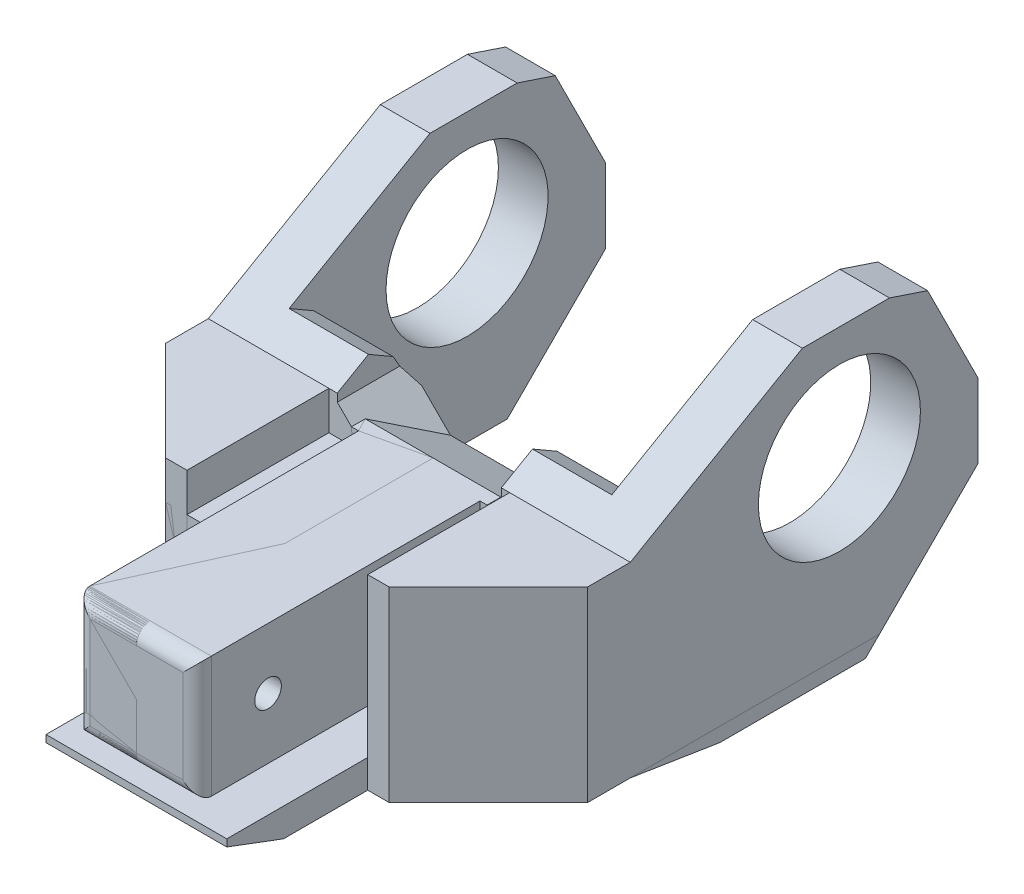
SolidWorks part; units mm, degrees
ref_plane "Front Plane" through (0, 0, 0) normal (0, 0, 1) x (1, 0, 0)
ref_plane "Top Plane" through (0, 0, 0) normal (0, 1, 0) x (1, 0, 0)
ref_plane "Right Plane" through (0, 0, 0) normal (1, 0, 0) x (0, 0, -1)
sketch "Sketch1" plane through (0, 0, 0) normal (0, 1, 0) x (1, 0, 0)
  line L2 (0, 0) -> (0, 40)
  line L3 (0, 40) -> (21.73, 40)
  line L4 (21.73, 0) -> (21.73, 40)
  line L5 (-1.5, 40) -> (23.23, 40)
  line L6 (-1.5, 40) -> (-1.5, 45)
  line L7 (-1.5, 45) -> (23.23, 45)
  line L8 (23.23, 40) -> (23.23, 45)
  line L10 (0, 0) -> (0, -10.6333)
  line L11 (0, -10.6333) -> (21.73, -10.6333)
  line L12 (21.73, 0) -> (21.73, -10.6333)
  dimension "D1" = 21.73
  dimension "D3" = 1.5
  dimension "D4" = 1.5
  dimension "D5" = 5
extrude "Boss-Extrude1" add sketch "Sketch1" along normal blind 21.73 contours L5 L8 L7 L6 L3 | L4 L3 L2 region at (10.865, 0, -14.6834) region at (10.865, 0, -42.5)
extrude "Boss-Extrude2" add sketch "Sketch1<4>" against normal blind 1.5 and the other way blind 23.23 contours L5 L8 L7 L6 L3 region at (10.865, 0, -42.5)
sketch "Sketch1<4>" plane through (0, 0, 0) normal (0, 1, 0) x (1, 0, 0) same geometry as "Sketch1"
sketch "Sketch2" plane through (23.23, 0, 0) normal (1, 0, 0) x (0, 0, -1)
  line L0 (40, -1.5) -> (45, -1.5) construction
  line L1 (40, 23.23) -> (59.05, 23.23)
  line L2 (40, 23.23) -> (40, -1.5)
  line L3 (40, -1.5) -> (59.05, -1.5)
  line L4 (59.05, 23.23) -> (59.05, -1.5)
  dimension "D1" = 19.05
extrude "Boss-Extrude3" add sketch "Sketch2" along normal blind 25.4
sketch "Sketch3" plane through (0, 0, -59.05) normal (0, 0, -1) x (-1, 0, 0)
  line L0 (-48.63, -1.5) -> (-23.23, -1.5) construction
  line L1 (-48.63, 23.23) -> (-42.28, 23.23)
  line L2 (-48.63, 23.23) -> (-48.63, -1.5)
  line L3 (-48.63, -1.5) -> (-42.28, -1.5)
  line L4 (-42.28, 23.23) -> (-42.28, -1.5)
  dimension "D1" = 6.35
extrude "Boss-Extrude4" add sketch "Sketch3" along normal blind 43.18
sketch "Sketch4" plane through (0, 0, -59.05) normal (0, 0, -1) x (-1, 0, 0)
  line L1 (-42.28, -1.5) -> (-23.23, -1.5)
  line L2 (-42.28, -1.5) -> (-42.28, 23.23)
  line L3 (-42.28, 23.23) -> (-23.23, 23.23)
  line L4 (-23.23, -1.5) -> (-23.23, 23.23)
extrude "Cut-Extrude1" cut sketch "Sketch4" against normal up to vertex (14.05 mm away) up to point (23.23, -1.5, -45)
sketch "Sketch5" plane through (0, 0, -45) normal (0, 0, -1) x (-1, 0, 0)
  line L1 (-42.28, 23.23) -> (1.5, 23.23)
  line L2 (-42.28, 23.23) -> (-42.28, -1.5)
  line L3 (-42.28, -1.5) -> (1.5, -1.5)
  line L4 (1.5, 23.23) -> (1.5, -1.5)
extrude "Boss-Extrude5" add sketch "Sketch5" along normal blind 7.62
sketch "Sketch6" plane through (0, -1.5, 0) normal (0, -1, 0) x (1, 0, 0)
  line L0 (48.63, -40) -> (48.63, -102.23) construction
  line L1 (-1.5, -40) -> (48.63, -40)
  line L2 (-1.5, -40) -> (-1.5, -52.62)
  line L3 (-1.5, -52.62) -> (42.28, -52.62)
  line L4 (48.63, -40) -> (48.63, -46.27)
  line L6 (48.63, -102.23) -> (42.28, -102.23)
  line L7 (48.63, -102.23) -> (48.63, -46.27)
  line L9 (42.28, -102.23) -> (42.28, -52.62)
extrude "Boss-Extrude6" add sketch "Sketch6" along normal blind 8.79
sketch "Sketch7" plane through (0, 23.23, 0) normal (0, 1, 0) x (1, 0, 0)
  line L0 (48.63, 102.23) -> (48.63, 40) construction
  line L1 (-1.5, 40) -> (48.63, 40)
  line L2 (-1.5, 40) -> (-1.5, 52.62)
  line L3 (-1.5, 52.62) -> (42.28, 52.62)
  line L4 (48.63, 40) -> (48.63, 46.27)
  line L5 (-1.5, 52.62) -> (42.28, 52.62) construction
  line L7 (42.28, 102.23) -> (48.63, 102.23)
  line L8 (42.28, 102.23) -> (42.28, 52.62)
  line L10 (48.63, 102.23) -> (48.63, 46.27)
extrude "Boss-Extrude7" add sketch "Sketch7" along normal blind 20.22
sketch "Sketch9" plane through (42.28, 0, 0) normal (-1, 0, 0) x (0, 0, 1)
  line L1 (-102.23, 43.45) -> (-52.62, 43.45)
  line L2 (-102.23, 43.45) -> (-102.23, -10.29)
  line L3 (-102.23, -10.29) -> (-52.62, -10.29)
  line L4 (-52.62, 43.45) -> (-52.62, -10.29)
extrude "Boss-Extrude8" add sketch "Sketch9" along normal blind 2.54
sketch "Sketch10" plane through (39.74, 0, 0) normal (-1, 0, 0) x (0, 0, 1)
  line L0 (-77.425, 43.45) -> (-77.425, 23.13)
  line L1 (-52.62, 43.45) -> (-102.23, 43.45) construction
  circle A0 centre (-77.425, 23.13) radius 14.5
  dimension "D1" = 29
  dimension "D2" = 20.32
extrude "Cut-Extrude2" cut sketch "Sketch10" against normal blind 44.704 contours A0 region at (39.74, 13.167, -87.388)
sketch "Sketch11" plane through (0, 0, 10.6333) normal (0, 0, 1) x (1, 0, 0)
  line L6 (0, 0) -> (21.73, 0) construction
  line L7 (0, 21.73) -> (0, 0) construction
  circle A0 centre (2.54, 2.54) radius 1.778
  dimension "D1" = 3.556
  dimension "D3" = 2.54
  dimension "D2" = 2.54
fillet "Fillet3" radius 2.54 4 edges at (10.865, 0, 10.6333) (0, 10.865, 10.6333) (10.865, 21.73, 10.6333) (21.73, 10.865, 10.6333)
chamfer "Chamfer1" distance 20.16 angle 45 1 edges at (44.185, -10.29, -102.23)
chamfer "Chamfer2" distance 20.32 distance2 10.16 1 edges at (44.185, 43.45, -102.23) first distance on face at (44.185, 26.66, -102.23)
sketch "Sketch12" plane through (0, 0, -40) normal (0, 0, 1) x (1, 0, 0)
  line L0 (-1.5, 43.45) -> (-1.5, -10.29) construction
  line L1 (-1.5, 21.73) -> (21.73, 21.73)
  line L2 (-1.5, 21.73) -> (-1.5, 43.45)
  line L3 (-1.5, 43.45) -> (21.73, 43.45)
  line L4 (21.73, 21.73) -> (21.73, 43.45)
  line L5 (-1.5, 43.45) -> (48.63, 43.45) construction
extrude "Cut-Extrude4" cut sketch "Sketch12" against normal blind 23.114
sketch "Sketch13" plane through (21.73, 0, 0) normal (-1, 0, 0) x (0, 0, 1)
  line L1 (-52.62, 43.45) -> (-40, 43.45)
  line L2 (-52.62, 43.45) -> (-52.62, 21.73)
  line L3 (-52.62, 21.73) -> (-40, 21.73)
  line L4 (-40, 43.45) -> (-40, 21.73)
extrude "Cut-Extrude5" cut sketch "Sketch13" against normal blind 3.81
chamfer "Chamfer4" distance 2.54 angle 45 1 edges at (25.54, 21.73, -46.31)
chamfer "Chamfer7" distance 17.78 angle 60 1 edges at (37.085, 43.45, -40) first distance on face at (19.2545, 16.1373, -40)
chamfer "Chamfer8" distance 2.54 angle 81 1 edges at (23.565, -10.29, -40) first distance on face at (19.2545, 12.9045, -40)
chamfer "Chamfer10" distance 12.7 distance2 6.35 1 edges at (39.74, 11.6037, -52.62) first distance on face at (21.5086, 16.3064, -52.62)
sketch "Sketch16" plane through (0, 0, -40) normal (0, 0, 1) x (1, 0, 0)
  line L0 (-1.5, -7.75) -> (48.63, -7.75) construction
  line L1 (48.63, 25.67) -> (27.04, 25.67)
  line L2 (48.63, 25.67) -> (48.63, -7.75)
  line L3 (48.63, -7.75) -> (27.04, -7.75)
  line L4 (27.04, 25.67) -> (27.04, -7.75)
  dimension "D1" = 21.59
extrude "Boss-Extrude9" add sketch "Sketch16" along normal blind 25.4
sketch "Sketch17" plane through (-1.5, 0, 0) normal (-1, 0, 0) x (0, 0, 1)
  line L0 (-52.62, 21.73) -> (-52.62, -9.7488)
  line L1 (-52.62, -9.7488) -> (-40, -7.75)
  line L2 (-40, -7.75) -> (-40, 21.73)
  line L3 (-40, 21.73) -> (-52.62, 21.73)
extrude "Boss-Extrude10" add sketch "Sketch17" along normal blind 25.4
chamfer "Chamfer12" distance 5.08 distance2 10.16 1 edges at (-1.95, 21.73, -52.62) first distance on face at (10.6229, 16.3064, -52.62)
chamfer "Chamfer13" distance 2.54 angle 45 1 edges at (44.185, 43.45, -92.07) first distance on face at (44.185, 33.29, -97.15)
sketch "Sketch18" plane through (0, 0, -40) normal (0, 0, 1) x (1, 0, 0)
  line L0 (-26.9, 21.73) -> (0, 21.73) construction
  line L1 (-26.9, -7.75) -> (-2.77, -7.75)
  line L2 (-26.9, -7.75) -> (-26.9, 21.73)
  line L3 (-26.9, 21.73) -> (-2.77, 21.73)
  line L4 (-2.77, -7.75) -> (-2.77, 21.73)
  dimension "D1" = 24.13
extrude "Boss-Extrude11" add sketch "Sketch18" along normal blind 25.4
extrude "Cut-Extrude9" cut sketch "Sketch11" against normal through all
chamfer "Chamfer14" distance 17.78 angle 45 2 edges at (48.63, 8.96, -14.6) (-26.9, 6.99, -14.6)
sketch "Sketch19" plane through (0, 0, -40) normal (0, 0, 1) x (1, 0, 0)
  line L0 (27.04, 25.67) -> (27.04, -7.75) construction
  line L1 (-2.77, -7.75) -> (27.04, -7.75)
  line L2 (-2.77, -7.75) -> (-2.77, -2.67)
  line L3 (-2.77, -2.67) -> (27.04, -2.67)
  line L4 (27.04, -7.75) -> (27.04, -2.67)
  dimension "D1" = 5.08
extrude "Boss-Extrude12" add sketch "Sketch19" along normal through all
chamfer "Chamfer15" distance 10.16 distance2 3.81 1 edges at (12.135, -7.75, 10.6333) first distance on face at (11.373, -7.75, -18.1893)
sketch "Sketch20" plane through (0, 0, 0) normal (-1, 0, 0) x (0, 0, 1)
  line L0 (8.0933, 21.73) -> (-2.0667, 21.73)
  line L1 (8.0933, 21.73) -> (-40, 21.73) construction
  line L2 (-2.0667, 21.73) -> (-2.0667, 10.865)
  line L3 (-2.0667, 10.865) -> (8.0933, 10.865)
  line L4 (8.0933, 0) -> (8.0933, 21.73) construction
  circle A0 centre (-2.0667, 10.865) radius 2.3812
  dimension "D1" = 4.7625
  dimension "D2" = 10.16
extrude "Cut-Extrude10" cut sketch "Sketch20" against normal through all contours L2 A0 L3 | L3 A0 L2 region at (0, 11.8756, -1.0561) region at (0, 10.5281, -2.4036)
sketch "Sketch21" plane through (0, 0, -40) normal (0, 0, -1) x (-1, 0, 0)
  line L1 (2.77, 21.73) -> (26.9, 21.73)
  line L2 (2.77, 21.73) -> (2.77, 18.7814)
  line L3 (2.77, 18.7814) -> (26.9, 18.7814)
  line L4 (26.9, 21.73) -> (26.9, 18.7814)
extrude "Cut-Extrude11" cut sketch "Sketch21" against normal up to surface (25.4 mm away) up to face at (-5.31, 5.058, -14.6)
sketch "Sketch22" plane through (-26.9, 0, 0) normal (-1, 0, 0) x (0, 0, 1)
  line L0 (-40, 18.7814) -> (-52.62, 10.0359)
  line L1 (-52.62, 16.65) -> (-52.62, -9.7488) construction
  line L2 (-52.62, 10.0359) -> (-52.62, 16.65)
  line L3 (-52.62, 16.65) -> (-40, 18.7814)
extrude "Cut-Extrude12" [suppressed] cut sketch "Sketch22" against normal up to surface (50.13 mm away) up to face at (33.4868, 7.8499, -55.8434)
ref_plane "Plane2" through (0, -7.75, 0) normal (0, -1, 0) x (-1, 0, 0)
split "Split1" trim tools "Plane2" bodies to split 124 resulting bodies 126 127
sketch "Sketch23" plane through (0, 21.73, 0) normal (0, 1, 0) x (1, 0, 0)
  line L0 (10.865, -8.0933) -> (10.865, 44.5325)
  line L1 (0, -8.0933) -> (21.73, -8.0933) construction
  line L2 (23, 50.6) -> (6.72, 42.46) construction
split line "Split Line1"
ref_plane "Plane3" through (10.865, 0, 0) normal (-1, 0, 0) x (0, 0, 1)
split "Split2" trim tools "Plane3" bodies to split 128 resulting bodies 129 130
mirror "Mirror2" about plane through (10.865, 0, 0) normal (-1, 0, 0) of bodies 129
combine bodies "Combine1" operation type add bodies to combine 131 129
sketch "Sketch24" plane through (0, 1.932, 1.1154) normal (0, 0.866, 0.5) x (1, 0, 0)
  line L0 (-3.81, 62.0483) -> (-3.81, 56.4603)
  line L1 (-3.81, 47.476) -> (-3.81, 62.0483) construction
  line L2 (-3.81, 56.4603) -> (-18.01, 56.4603)
  line L3 (-18.01, 56.4603) -> (-18.01, 69.3807)
  line L4 (-18.01, 69.3807) -> (-5.31, 62.0483)
  line L5 (-5.31, 62.0483) -> (-3.81, 62.0483)
  dimension "D1" = 5.588
extrude "Cut-Extrude13" cut sketch "Sketch24" against normal blind 26.67
mirror "Mirror3" about plane through (10.865, 0, 0) normal (-1, 0, 0) of "Cut-Extrude13"
sketch "Sketch25" plane through (25.54, 0, 0) normal (1, 0, 0) x (0, 0, -1)
  line L0 (52.62, 21.7802) -> (51.1825, 24.27)
  line L1 (51.1825, 24.27) -> (52.62, 24.27)
  line L2 (52.62, 24.27) -> (52.62, 21.7802)
extrude "Cut-Extrude14" cut sketch "Sketch25" against normal blind 31.496
chamfer "Chamfer17" distance 2.54 angle 60 1 edges at (32.64, 30.1622, -47.7807) first distance on face at (36.4086, 32.0335, -51.0219)
chamfer "Chamfer18" distance 2.54 angle 60 1 edges at (-10.91, 30.1622, -47.7807) first distance on face at (-14.6786, 32.0335, -51.0219)
